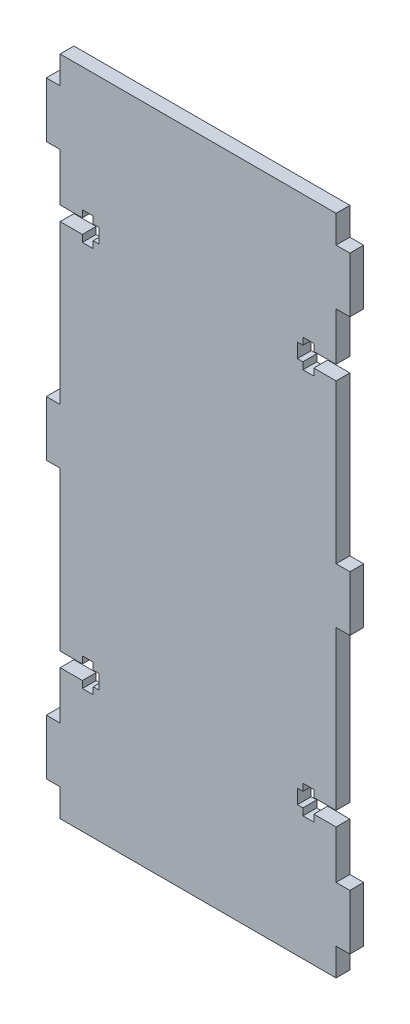
SolidWorks part; units mm, degrees
ref_plane "Front Plane" through (0, 0, 0) normal (0, 0, 1) x (1, 0, 0)
ref_plane "Top Plane" through (0, 0, 0) normal (0, 1, 0) x (1, 0, 0)
ref_plane "Right Plane" through (0, 0, 0) normal (1, 0, 0) x (0, 0, -1)
sketch "Sketch1" plane through (0, 0, 0) normal (0, 0, 1) x (1, 0, 0)
  line L1 (0, 0) -> (63.5, 0)
  line L2 (0, 0) -> (0, 152.4)
  line L3 (0, 152.4) -> (63.5, 152.4)
  line L4 (63.5, 0) -> (63.5, 152.4)
  dimension "D1" = 152.4
  dimension "D2" = 63.5
extrude "Boss-Extrude1" add sketch "Sketch1" along normal blind 3.175
sketch "Sketch2" plane through (0, 0, 3.175) normal (0, 0, 1) x (1, 0, 0)
  line L0 (0, 76.2) -> (63.5, 76.2) construction
  line L1 (0, 146.05) -> (-3.175, 146.05)
  line L2 (0, 146.05) -> (0, 133.35)
  line L3 (0, 133.35) -> (-3.175, 133.35)
  line L4 (-3.175, 146.05) -> (-3.175, 133.35)
  line L5 (0, 6.35) -> (-3.175, 6.35)
  line L6 (0, 6.35) -> (0, 19.05)
  line L7 (0, 19.05) -> (-3.175, 19.05)
  line L8 (-3.175, 6.35) -> (-3.175, 19.05)
  line L9 (0, 152.4) -> (0, 0) construction
  line L10 (63.5, 0) -> (63.5, 152.4) construction
  line L11 (-3.175, 76.2) -> (0, 76.2) construction
  line L12 (0, 82.55) -> (-3.175, 82.55)
  line L13 (0, 82.55) -> (0, 69.85)
  line L14 (0, 69.85) -> (-3.175, 69.85)
  line L15 (-3.175, 82.55) -> (-3.175, 69.85)
  line L16 (31.75, 152.4) -> (31.75, 0) construction
  line L17 (63.5, 152.4) -> (0, 152.4) construction
  line L18 (0, 0) -> (63.5, 0) construction
  line L19 (66.675, 146.05) -> (66.675, 133.35)
  line L20 (63.5, 133.35) -> (66.675, 133.35)
  line L21 (63.5, 146.05) -> (63.5, 133.35)
  line L22 (63.5, 146.05) -> (66.675, 146.05)
  line L23 (0, 82.55) -> (-3.175, 82.55)
  line L24 (0, 69.85) -> (-3.175, 69.85)
  line L25 (0, 82.55) -> (-3.175, 82.55)
  line L26 (0, 69.85) -> (-3.175, 69.85)
  line L27 (0, 82.55) -> (-3.175, 82.55)
  line L28 (0, 69.85) -> (-3.175, 69.85)
  line L29 (66.675, 6.35) -> (66.675, 19.05)
  line L30 (63.5, 19.05) -> (66.675, 19.05)
  line L31 (63.5, 6.35) -> (63.5, 19.05)
  line L32 (63.5, 6.35) -> (66.675, 6.35)
  line L33 (0, 82.55) -> (-3.175, 82.55)
  line L34 (0, 69.85) -> (-3.175, 69.85)
  line L35 (0, 82.55) -> (-3.175, 82.55)
  line L36 (0, 69.85) -> (-3.175, 69.85)
  line L37 (0, 82.55) -> (-3.175, 82.55)
  line L38 (0, 69.85) -> (-3.175, 69.85)
  line L39 (0, 82.55) -> (-3.175, 82.55)
  line L40 (0, 69.85) -> (-3.175, 69.85)
  line L41 (66.675, 76.2) -> (63.5, 76.2) construction
  line L42 (63.5, 69.85) -> (66.675, 69.85)
  line L43 (63.5, 82.55) -> (66.675, 82.55)
  line L44 (63.5, 69.85) -> (66.675, 69.85)
  line L45 (63.5, 82.55) -> (66.675, 82.55)
  line L46 (63.5, 69.85) -> (66.675, 69.85)
  line L47 (63.5, 82.55) -> (66.675, 82.55)
  line L48 (63.5, 69.85) -> (66.675, 69.85)
  line L49 (63.5, 82.55) -> (66.675, 82.55)
  line L50 (63.5, 69.85) -> (66.675, 69.85)
  line L51 (63.5, 82.55) -> (66.675, 82.55)
  line L52 (63.5, 69.85) -> (66.675, 69.85)
  line L53 (63.5, 82.55) -> (66.675, 82.55)
  line L54 (63.5, 69.85) -> (66.675, 69.85)
  line L55 (63.5, 82.55) -> (66.675, 82.55)
  line L56 (66.675, 82.55) -> (66.675, 69.85)
  line L57 (63.5, 69.85) -> (66.675, 69.85)
  line L58 (63.5, 82.55) -> (63.5, 69.85)
  line L59 (63.5, 82.55) -> (66.675, 82.55)
  line M1 (0, 152.4) -> (0, 0)
  line M3 (63.5, 0) -> (63.5, 152.4)
  dimension "D1" = 3.175
  dimension "D2" = 12.7
  dimension "D3" = 12.7
  dimension "D4" = 12.7
  dimension "D5" = 3.175
  dimension "D6" = 6.35
  dimension "D7" = 6.35
extrude "Boss-Extrude3" add sketch "Sketch2" against normal blind 3.175 contours L12 L15 L14 M1 | L22 L20 L19 M3 | L56 L43 L42 M3 | L32 L29 L30 M3 | L8 L5 L7 M1 | L4 L3 L2 L1 region at (-1.5875, 12.7, 3.175) region at (-1.5875, 76.2, 3.175) region at (65.0875, 12.7, 3.175) region at (65.0875, 76.2, 3.175) region at (65.0875, 139.7, 3.175)
sketch "Sketch4" plane through (0, 0, 3.175) normal (0, 0, 1) x (1, 0, 0)
  line L0 (31.75, 152.4) -> (31.75, 0) construction
  line L1 (63.5, 152.4) -> (0, 152.4) construction
  line L2 (0, 0) -> (63.5, 0) construction
  line L3 (0, 133.35) -> (0, 82.55) construction
  line L4 (0, 122.301) -> (8.89, 122.301)
  line L5 (0, 122.301) -> (0, 118.999)
  line L6 (0, 118.999) -> (8.89, 118.999)
  line L7 (8.89, 122.301) -> (8.89, 118.999)
  line L8 (5.12, 120.65) -> (7.62, 120.65) construction
  line L9 (5.12, 123.9) -> (7.62, 123.9)
  line L10 (5.12, 123.9) -> (5.12, 117.4)
  line L11 (5.12, 117.4) -> (7.62, 117.4)
  line L12 (7.62, 123.9) -> (7.62, 117.4)
  line L13 (0, 120.65) -> (8.89, 120.65) construction
  line L14 (0, 133.35) -> (-3.175, 133.35) construction
  line L15 (-3.175, 76.2) -> (66.675, 76.2) construction
  line L16 (-3.175, 82.55) -> (-3.175, 69.85) construction
  line L17 (66.675, 82.55) -> (66.675, 69.85) construction
  line L18 (0, 31.75) -> (8.89, 31.75) construction
  line L19 (5.12, 31.75) -> (7.62, 31.75) construction
  line L20 (7.62, 28.5) -> (7.62, 35)
  line L21 (5.12, 35) -> (7.62, 35)
  line L22 (5.12, 28.5) -> (5.12, 35)
  line L23 (5.12, 28.5) -> (7.62, 28.5)
  line L24 (8.89, 30.099) -> (8.89, 33.401)
  line L25 (0, 33.401) -> (8.89, 33.401)
  line L26 (0, 30.099) -> (0, 33.401)
  line L27 (0, 30.099) -> (8.89, 30.099)
  line L28 (58.38, 31.75) -> (55.88, 31.75) construction
  line L29 (63.5, 31.75) -> (54.61, 31.75) construction
  line L30 (63.5, 120.65) -> (54.61, 120.65) construction
  line L31 (58.38, 120.65) -> (55.88, 120.65) construction
  line L32 (63.5, 30.099) -> (54.61, 30.099)
  line L33 (63.5, 30.099) -> (63.5, 33.401)
  line L34 (63.5, 33.401) -> (54.61, 33.401)
  line L35 (54.61, 30.099) -> (54.61, 33.401)
  line L36 (58.38, 28.5) -> (55.88, 28.5)
  line L37 (58.38, 28.5) -> (58.38, 35)
  line L38 (58.38, 35) -> (55.88, 35)
  line L39 (55.88, 28.5) -> (55.88, 35)
  line L40 (55.88, 123.9) -> (55.88, 117.4)
  line L41 (58.38, 117.4) -> (55.88, 117.4)
  line L42 (58.38, 123.9) -> (58.38, 117.4)
  line L43 (58.38, 123.9) -> (55.88, 123.9)
  line L44 (54.61, 122.301) -> (54.61, 118.999)
  line L45 (63.5, 118.999) -> (54.61, 118.999)
  line L46 (63.5, 122.301) -> (63.5, 118.999)
  line L47 (63.5, 122.301) -> (54.61, 122.301)
  dimension "D1" = 3.302
  dimension "D2" = 6.5
  dimension "D3" = 2.5
  dimension "D4" = 1.27
  dimension "D5" = 8.89
  dimension "D6" = 12.7
extrude "Cut-Extrude4" cut sketch "Sketch4" against normal blind 3.175 contours L6 L7 L4 L5 | L9 L12 L11 L10 | L21 L20 L23 L22 | L24 L25 L26 L27 | L35 L34 L33 L32 | L38 L39 L36 L37 | L41 L40 L43 L42 | L45 L44 L47 L46
